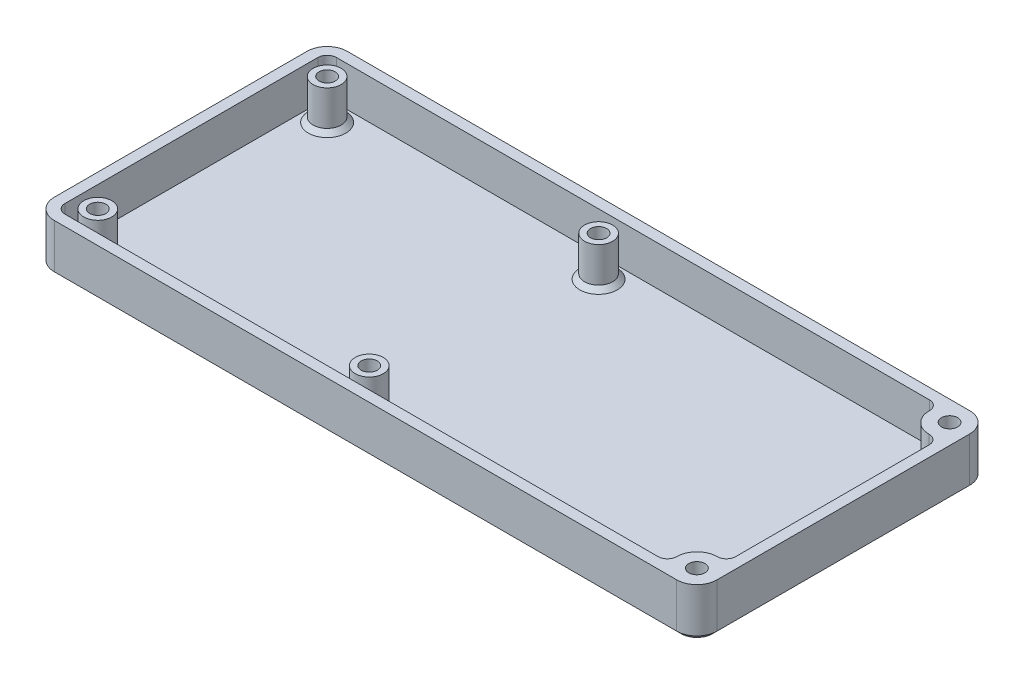
SolidWorks part; units mm, degrees
ref_plane "Front Plane" through (0, 0, 0) normal (0, 0, 1) x (1, 0, 0)
ref_plane "Top Plane" through (0, 0, 0) normal (0, 1, 0) x (1, 0, 0)
ref_plane "Right Plane" through (0, 0, 0) normal (1, 0, 0) x (0, 0, -1)
sketch "Sketch1" plane through (0, 0, 0) normal (0, 1, 0) x (1, 0, 0)
  line L0 (-71.5618, 3.106) -> (63.4382, 3.106) construction
  line L1 (-71.5618, 31.106) -> (63.4382, 31.106)
  line L2 (-71.5618, 31.106) -> (-71.5618, -24.894)
  line L3 (-71.5618, -24.894) -> (63.4382, -24.894)
  line L4 (63.4382, 31.106) -> (63.4382, -24.894)
  line L5 (-60.6618, -24.894) -> (-60.6618, -31.6828) construction
  line L6 (-68.0618, 27.606) -> (-10.0618, 27.606)
  line L7 (-68.0618, 27.606) -> (-68.0618, -21.394)
  line L8 (-68.0618, -21.394) -> (-10.0618, -21.394)
  line L9 (-10.0618, 27.606) -> (-10.0618, -21.394)
  line L10 (-39.5618, -24.894) -> (-39.5618, -31.6828) construction
  line L11 (-18.0618, -24.894) -> (-18.0618, -31.6828) construction
  line L12 (-65.4118, -26.5648) -> (-55.9118, -26.5648) construction
  line L13 (-48.0618, -26.5648) -> (-31.0618, -26.5648) construction
  line L14 (-22.0618, -26.5648) -> (-14.0618, -26.5648) construction
  line L15 (-72.5618, 9.606) -> (-72.5618, -3.394) construction
  line L16 (-71.5618, 3.106) -> (-72.5618, 3.106) construction
  dimension "D1" = 135
  dimension "D2" = 56
  dimension "D3" = 49
  dimension "D4" = 58
  dimension "D5" = 3.5
  dimension "D6" = 3.5
  dimension "D7" = 10.9
  dimension "D8" = 32
  dimension "D9" = 53.5
  dimension "D10" = 2
  dimension "D11" = 13
  dimension "D12" = 9.5
  dimension "D13" = 17
  dimension "D14" = 8
sketch "Sketch3" plane through (0, 0, 0) normal (0, 1, 0) x (1, 0, 0)
  line L4 (66.7382, 34.406) -> (-74.8618, 34.406)
  line L5 (-74.8618, 34.406) -> (-74.8618, -28.194)
  line L6 (-74.8618, -28.194) -> (66.7382, -28.194)
  line L7 (66.7382, -28.194) -> (66.7382, 34.406)
  line L8 (64.4382, 32.106) -> (-72.5618, 32.106)
  line L9 (64.4382, -25.894) -> (64.4382, 32.106)
  line L10 (-72.5618, -25.894) -> (64.4382, -25.894)
  line L11 (-72.5618, 32.106) -> (-72.5618, -25.894)
  line L12 (64.4382, 32.106) -> (-72.5618, 32.106)
  line L13 (64.4382, -25.894) -> (64.4382, 32.106)
  line L14 (-72.5618, -25.894) -> (64.4382, -25.894)
  line L15 (-72.5618, 32.106) -> (-72.5618, -25.894)
  line L16 (-4.0618, 3.106) -> (-4.0618, 34.406) construction
  line L17 (-71.5618, 3.106) -> (63.4382, 3.106) construction
  line L20 (-74.8618, 3.106) -> (52.7382, 3.106) construction
  line L25 (66.7382, -28.194) -> (66.7382, 34.406) construction
  line L26 (64.4382, -25.894) -> (64.4382, 32.106) construction
  dimension "D1" = 1
  dimension "D2" = 2.3
extrude "Boss-Extrude1" add sketch "Sketch3" along normal blind 10.5
sketch "Sketch5" plane through (0, 0, 0) normal (0, 1, 0) x (1, 0, 0)
  line L1 (-72.5618, 32.106) -> (64.4382, 32.106)
  line L2 (-72.5618, 32.106) -> (-72.5618, -25.894)
  line L3 (-72.5618, -25.894) -> (64.4382, -25.894)
  line L4 (64.4382, 32.106) -> (64.4382, -25.894)
extrude "Boss-Extrude2" add sketch "Sketch5" along normal blind 2
sketch "Sketch6" plane through (0, 2, 0) normal (0, 1, 0) x (1, 0, 0)
  circle A0 centre (-68.0618, 27.606) radius 3
  circle A1 centre (-68.0618, -21.394) radius 3
  circle A2 centre (-10.0618, -21.394) radius 3
  circle A3 centre (-10.0618, 27.606) radius 3
extrude "Boss-Extrude3" add sketch "Sketch6" along normal up to surface (8.5 mm away) up to face at (-4.0618, 10.5, -3.106)
sketch "Sketch10" plane through (0, 2, 0) normal (0, 1, 0) x (1, 0, 0)
  line L0 (64.4382, 32.106) -> (-72.5618, 32.106) construction
  line L1 (9.9382, 32.106) -> (11.9382, 32.106)
  line L2 (9.9382, 32.106) -> (9.9382, -25.894)
  line L3 (9.9382, -25.894) -> (11.9382, -25.894)
  line L4 (11.9382, 32.106) -> (11.9382, -25.894)
  line L5 (-72.5618, -25.894) -> (64.4382, -25.894) construction
  line L6 (-10.0618, 27.606) -> (-10.0618, -21.394) construction
  dimension "D1" = 2
  dimension "D2" = 20
sketch "Sketch11" plane through (0, 0, 28.194) normal (0, 0, 1) x (1, 0, 0)
  line L0 (-74.8618, 10.5) -> (-74.8618, 0) construction
  line L1 (-66.8618, 8.5) -> (-54.8618, 8.5)
  line L2 (-66.8618, 8.5) -> (-66.8618, 2.7)
  line L3 (-66.8618, 2.7) -> (-54.8618, 2.7)
  line L4 (-54.8618, 8.5) -> (-54.8618, 2.7)
  line L5 (-74.8618, 0) -> (66.7382, 0) construction
  line L6 (-60.8618, 8.5) -> (-60.6618, 0) construction
  line L7 (-65.4118, 0) -> (-55.9118, 0) construction
  line L9 (-47.778, 8.5) -> (-31.278, 8.5)
  line L10 (-47.778, 8.5) -> (-47.778, 5.7)
  line L11 (-47.778, 5.7) -> (-31.278, 5.7)
  line L12 (-31.278, 8.5) -> (-31.278, 5.7)
  line L13 (-68.0618, 0) -> (-10.0618, 0) construction
  line L14 (-39.5618, 0) -> (-39.528, 8.5) construction
  line L15 (-48.0618, 0) -> (-31.0618, 0) construction
  line L16 (-18.0618, 0) -> (-18.0618, 10.5) construction
  line L17 (-22.0618, 0) -> (-14.0618, 0) construction
  line L18 (-74.8618, 10.5) -> (66.7382, 10.5) construction
  circle A0 centre (-18.0618, 10.5) radius 3.1
  dimension "D5" = 6.2
  dimension "D1" = 2.7
  dimension "D2" = 12
  dimension "D3" = 5.7
  dimension "D4" = 16.5
  dimension "D6" = 8
  dimension "D7" = 5.8
  dimension "D8" = 2.8
sketch "Sketch12" plane through (-74.8618, 0, 0) normal (-1, 0, 0) x (0, 0, 1)
  line L0 (-3.106, 0) -> (-3.106, 10.5) construction
  line L1 (-27.606, 0) -> (21.394, 0) construction
  line L2 (-34.406, 10.5) -> (28.194, 10.5) construction
  line L3 (-24.106, 5.7) -> (17.894, 5.7)
  line L4 (-9.7329, 5.7) -> (3.7671, 5.7)
  line L5 (-9.7329, 5.7) -> (-9.7329, 2)
  line L6 (-9.7329, 2) -> (3.7671, 2)
  line L7 (3.7671, 5.7) -> (3.7671, 2)
  line L8 (-24.106, 10.5) -> (17.894, 10.5)
  line L9 (-24.106, 10.5) -> (-24.106, 5.7)
  line L10 (-34.406, 0) -> (28.194, 0) construction
  line L11 (17.894, 10.5) -> (17.894, 5.7)
  line L12 (-9.7329, 3.85) -> (3.7671, 3.85) construction
  point P17 (-3.106, 5.7)
  dimension "D1" = 13.5
  dimension "D2" = 5.7
  dimension "D3" = 3.7
  dimension "D4" = 2
fillet "Fillet6" radius 2 1 edges at (64.4382, 6.25, -32.106)
fillet "Fillet8" radius 2 2 edges at (-72.5618, 6.25, 25.894) (-72.5618, 6.25, -32.106)
chamfer "Chamfer1" distance 1 angle 45 4 edges at (-68.0618, 2, 24.394) (-10.0618, 2, 24.394) (-10.0618, 2, -24.606) (-68.0618, 2, -24.606)
sketch "Sketch24" plane through (0, 2, 0) normal (0, 1, 0) x (1, 0, 0)
  line L0 (15.8873, 3.0622) -> (61.5789, 3.0622) construction
  line L2 (66.7382, -28.194) -> (66.7382, 34.406) construction
  circle A0 centre (62.4382, -23.894) radius 4.3
  circle A1 centre (62.4382, 30.0183) radius 4.3
  dimension "D1" = 4.3
extrude "Boss-Extrude7" add sketch "Sketch24" along normal up to surface (8.5 mm away) up to face at (-4.0618, 10.5, -3.106)
fillet "Fillet21" radius 2 1 edges at (58.6317, 6.25, 25.894)
fillet "Fillet22" radius 2 3 edges at (64.4382, 6.25, 20.0874) (64.4382, 6.25, -26.2118) (58.679, 6.25, -32.106)
fillet "Fillet20" radius 4.3 4 edges at (66.7382, 5.25, 28.194) (-74.8618, 5.25, -34.406) (-74.8618, 5.25, 28.194) (66.7382, 5.25, -34.406)
hole_wizard "CSK for #4 Flat Head Socket Cap Screw1" positions "Sketch28" profile "Sketch27" countersink size "#4" standard "ANSI Inch"
sketch "Sketch28" plane through (0, 0, 0) normal (0, -1, 0) x (-1, 0, 0)
  point P0 (68.0618, 27.606)
  point P4 (68.0618, -21.394)
  point P8 (-62.4382, 30.106)
  point P12 (-62.4382, -23.894)
  point P15 (10.0618, -21.394)
  point P19 (10.0618, 27.606)
sketch "Sketch27" plane through (-68.0618, 0, -27.606) normal (1, 0, 0) x (0, 0, -1)
  line L0 (0, 0) -> (0, 15.0378)
  line L1 (0, 15.0378) -> (1.7272, 14)
  line L2 (1.7272, 14) -> (1.7272, 1.8805)
  line L3 (1.7272, 1.8805) -> (3.3619, 0)
  line L5 (3.3619, 0) -> (0, 0)
  line L6 (-1.7272, 1.8805) -> (-3.3619, 0) construction
  line L10 (0, 15.0378) -> (-1.7272, 14) construction
  line L11 (0, -6.35) -> (0, 107.95) construction
  dimension "Hole Dia." = 3.4544
  dimension "Hole Depth" = 14
  dimension "Near C'Sink Dia." = 6.7238
  dimension "Near C'Sink Angle" = 82
  dimension "Drill Angle" = 118
chamfer "Chamfer7" distance 1 angle 45 8 edges at (-74.8618, 0, -3.106) (-73.6023, 0, 26.9346) (-73.6023, 0, -33.1466) (-4.0618, 0, 28.194) (-4.0618, 0, -34.406) (65.4788, 0, 26.9346) (65.4788, 0, -33.1466) (66.7382, 0, -3.106)
